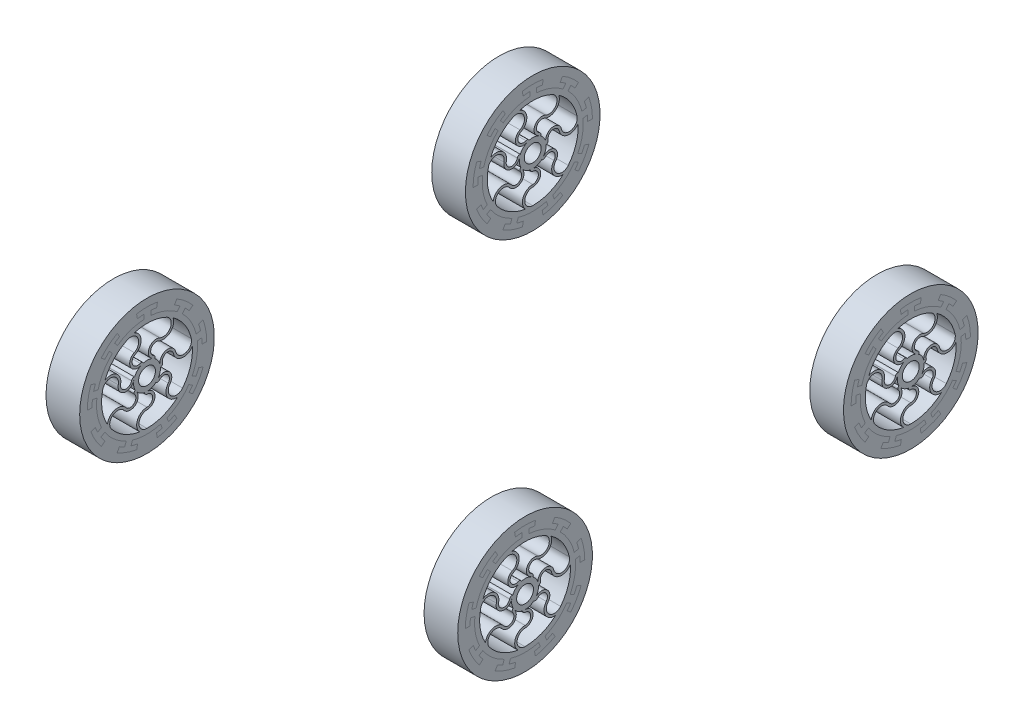
SolidWorks part; units mm, degrees
ref_plane "Front Plane" through (0, 0, 0) normal (0, 0, 1) x (1, 0, 0)
ref_plane "Top Plane" through (0, 0, 0) normal (0, 1, 0) x (1, 0, 0)
ref_plane "Right Plane" through (0, 0, 0) normal (1, 0, 0) x (0, 0, -1)
ref_plane "Plane1" through (64.95, 0, 0) normal (1, 0, 0) x (0, 0, -1)
sketch "Sketch1" plane through (64.95, 0, 0) normal (1, 0, 0) x (0, 0, -1)
  circle A0 centre (0, 0) radius 25.4 construction
  circle A1 centre (0, 0) radius 3.175
  circle A2 centre (0, 0) radius 5.08
  circle A3 centre (0, 0) radius 19.05
  circle A4 centre (0, 0) radius 17.145
  dimension "D1" = 50.8
  dimension "D2" = 38.1
  dimension "D3" = 34.29
  dimension "D4" = 6.35
  dimension "D5" = 10.16
extrude "Boss-Extrude1" add sketch "Sketch1" along normal blind 12.7 contours A3 A4 | A2 A1 region at (64.95, 0, 4.9363) region at (64.95, 0, 18.5112)
sketch "Sketch2" plane through (64.95, 0, 0) normal (1, 0, 0) x (0, 0, -1)
  circle A0 centre (0, 0) radius 5.08
  circle A1 centre (0, 0) radius 17.145
  arc A2 (0, -11.1125) -> (0, -5.08) centre (0, -8.0963) ccw
  arc A3 (0, -11.1125) -> (0, -17.145) centre (0, -14.1288) ccw
  arc A6 (0, -10.2235) -> (-2.7239, -16.9272) centre (0, -14.1288) ccw
  arc A7 (0, -10.2235) -> (0, -5.969) centre (0, -8.0963) ccw
  arc A8 (0, -5.969) -> (-0.8856, -5.0022) centre (0, -5.08) cw
  dimension "D1" = 10.16
  dimension "D2" = 34.29
  dimension "D3" = 0.889
  dimension "D4" = 0
extrude "Boss-Extrude2" add sketch "Sketch2" along normal up to surface (12.7 mm away) contours A8 A7 A6 A1 A3 A2 A0 region at (64.95, -10.6813, 0.5074) up to face at (77.65, 0, -3.175)
pattern_circular "CirPattern1" count 7 over 360 about axis through (77.65, 0, 0) along (1, 0, 0) of "Boss-Extrude2"
sketch "Sketch3" plane through (64.95, 0, 0) normal (1, 0, 0) x (0, 0, -1)
  line L2 (-3.9449, 22.1713) -> (-3.6335, 20.4208)
  line L4 (-1.1102, 20.7118) -> (-1.1102, 19.0176)
  line L6 (3.9449, 22.1713) -> (3.6335, 20.4208)
  line L7 (1.4298, 20.6921) -> (1.4298, 18.9963)
  circle A0 centre (0, 0) radius 19.05 construction
  circle A1 centre (0, 0) radius 19.05
  arc A2 (-3.9449, 22.1713) -> (3.9449, 22.1713) centre (0, 0) cw
  arc A3 (-3.6335, 20.4208) -> (-1.1102, 20.7118) centre (0, 0) cw
  arc A4 (1.4298, 20.6921) -> (3.6335, 20.4208) centre (0, 0) cw
  dimension "D5" = 2.5401
  dimension "D1" = 2.54
  dimension "D2" = 1.778
  dimension "D3" = 2.54
  dimension "D4" = 3.175
extrude "Boss-Extrude3" add sketch "Sketch3" along a picked direction on the side of the normal blind 12.7 contours A1 L7 L6 A2 L2 A3 L4 region at (64.95, 21.1336, -0.0386)
pattern_circular "CirPattern2" count 9 over 360 about axis through (77.65, 0, 0) along (1, 0, 0) of "Boss-Extrude3"
sketch "Sketch5" plane through (64.95, 0, 0) normal (1, 0, 0) x (0, 0, -1)
  line L36 (-1.1102, 20.7118) -> (-1.1102, 19.0176)
  line L37 (-3.9449, 22.1713) -> (-3.6335, 20.4208)
  line L38 (3.6335, 20.4208) -> (3.9449, 22.1713)
  line L39 (1.4298, 18.9963) -> (1.4298, 20.6921)
  line L40 (12.4628, 16.5797) -> (11.3738, 15.282)
  line L41 (11.2294, 19.5199) -> (10.3428, 17.9787)
  line L42 (15.9096, 13.3077) -> (17.2734, 14.4484)
  line L43 (13.3059, 13.6329) -> (14.396, 14.932)
  line L44 (20.2043, 4.6899) -> (18.5359, 4.3957)
  line L45 (21.1494, 7.735) -> (19.4796, 7.1243)
  line L46 (20.7415, -0.0322) -> (22.5195, -0.035)
  line L47 (18.956, 1.8906) -> (20.6261, 2.1851)
  line L48 (18.492, -9.3944) -> (17.0248, -8.5474)
  line L49 (21.1733, -7.6692) -> (19.5016, -7.0637)
  line L50 (15.8682, -13.357) -> (17.2284, -14.502)
  line L51 (15.7363, -10.7364) -> (17.205, -11.5843)
  line L52 (8.1271, -19.083) -> (7.5476, -17.491)
  line L53 (11.29, -19.4849) -> (10.3986, -17.9465)
  line L54 (3.57, -20.432) -> (3.876, -22.1834)
  line L55 (5.1535, -18.3397) -> (5.7335, -19.9333)
  line L56 (-6.0406, -19.8424) -> (-5.4612, -18.2504)
  line L57 (-3.876, -22.1834) -> (-3.57, -20.432)
  line L58 (-10.3986, -17.9465) -> (-11.29, -19.4849)
  line L59 (-7.8407, -17.3616) -> (-8.4207, -18.9552)
  line L60 (-17.3818, -11.3173) -> (-15.9147, -10.4703)
  line L61 (-17.2284, -14.502) -> (-15.8682, -13.357)
  line L62 (-19.5016, -7.0637) -> (-21.1733, -7.6692)
  line L63 (-17.1662, -8.2599) -> (-18.6348, -9.1078)
  line L64 (-20.5899, 2.5032) -> (-18.9215, 2.2091)
  line L65 (-22.5195, -0.035) -> (-20.7415, -0.0322)
  line L66 (-19.4796, 7.1243) -> (-21.1494, 7.735)
  line L67 (-18.4594, 4.7068) -> (-20.1295, 5.0013)
  line L68 (-14.1637, 15.1525) -> (-13.0747, 13.8547)
  line L69 (-17.2734, 14.4484) -> (-15.9096, 13.3077)
  line L70 (-10.3428, 17.9787) -> (-11.2294, 19.5199)
  line L71 (-11.1153, 15.4711) -> (-12.2054, 16.7702)
  line L72 (-1.1102, 20.7118) -> (-1.1102, 19.0176)
  line L73 (-3.9449, 22.1713) -> (-3.6335, 20.4208)
  line L74 (3.6335, 20.4208) -> (3.9449, 22.1713)
  line L75 (1.4298, 18.9963) -> (1.4298, 20.6921)
  line L76 (12.4628, 16.5797) -> (11.3738, 15.282)
  line L77 (11.2294, 19.5199) -> (10.3428, 17.9787)
  line L78 (15.9096, 13.3077) -> (17.2734, 14.4484)
  line L79 (13.3059, 13.6329) -> (14.396, 14.932)
  line L80 (20.2043, 4.6899) -> (18.5359, 4.3957)
  line L81 (21.1494, 7.735) -> (19.4796, 7.1243)
  line L82 (20.7415, -0.0322) -> (22.5195, -0.035)
  line L83 (18.956, 1.8906) -> (20.6261, 2.1851)
  line L84 (18.492, -9.3944) -> (17.0248, -8.5474)
  line L85 (21.1733, -7.6692) -> (19.5016, -7.0637)
  line L86 (15.8682, -13.357) -> (17.2284, -14.502)
  line L87 (15.7363, -10.7364) -> (17.205, -11.5843)
  line L88 (8.1271, -19.083) -> (7.5476, -17.491)
  line L89 (11.29, -19.4849) -> (10.3986, -17.9465)
  line L90 (3.57, -20.432) -> (3.876, -22.1834)
  line L91 (5.1535, -18.3397) -> (5.7335, -19.9333)
  line L92 (-6.0406, -19.8424) -> (-5.4612, -18.2504)
  line L93 (-3.876, -22.1834) -> (-3.57, -20.432)
  line L94 (-10.3986, -17.9465) -> (-11.29, -19.4849)
  line L95 (-7.8407, -17.3616) -> (-8.4207, -18.9552)
  line L96 (-17.3818, -11.3173) -> (-15.9147, -10.4703)
  line L97 (-17.2284, -14.502) -> (-15.8682, -13.357)
  line L98 (-19.5016, -7.0637) -> (-21.1733, -7.6692)
  line L99 (-17.1662, -8.2599) -> (-18.6348, -9.1078)
  line L100 (-20.5899, 2.5032) -> (-18.9215, 2.2091)
  line L101 (-22.5195, -0.035) -> (-20.7415, -0.0322)
  line L102 (-19.4796, 7.1243) -> (-21.1494, 7.735)
  line L103 (-18.4594, 4.7068) -> (-20.1295, 5.0013)
  line L104 (-14.1637, 15.1525) -> (-13.0747, 13.8547)
  line L105 (-17.2734, 14.4484) -> (-15.9096, 13.3077)
  line L106 (-10.3428, 17.9787) -> (-11.2294, 19.5199)
  line L107 (-11.1153, 15.4711) -> (-12.2054, 16.7702)
  circle A0 centre (0, 0) radius 25.4
  arc A37 (-1.1102, 19.0176) -> (-11.1153, 15.4711) centre (0, 0) ccw
  arc A38 (-1.1102, 20.7118) -> (-3.6335, 20.4208) centre (0, 0) ccw
  arc A39 (3.9449, 22.1713) -> (-3.9449, 22.1713) centre (0, 0) ccw
  arc A40 (3.6335, 20.4208) -> (1.4298, 20.6921) centre (0, 0) ccw
  arc A41 (11.3738, 15.282) -> (1.4298, 18.9963) centre (0, 0) ccw
  arc A42 (12.4628, 16.5797) -> (10.3428, 17.9787) centre (0, 0) ccw
  arc A43 (17.2734, 14.4484) -> (11.2294, 19.5199) centre (0, 0) ccw
  arc A44 (15.9096, 13.3077) -> (14.396, 14.932) centre (0, 0) ccw
  arc A45 (18.5359, 4.3957) -> (13.3059, 13.6329) centre (0, 0) ccw
  arc A46 (20.2043, 4.6899) -> (19.4796, 7.1243) centre (0, 0) ccw
  arc A47 (22.5195, -0.035) -> (21.1494, 7.735) centre (0, 0) ccw
  arc A48 (20.7415, -0.0322) -> (20.6261, 2.1851) centre (0, 0) ccw
  arc A49 (17.0248, -8.5474) -> (18.956, 1.8906) centre (0, 0) ccw
  arc A50 (18.492, -9.3944) -> (19.5016, -7.0637) centre (0, 0) ccw
  arc A51 (17.2284, -14.502) -> (21.1733, -7.6692) centre (0, 0) ccw
  arc A52 (15.8682, -13.357) -> (17.205, -11.5843) centre (0, 0) ccw
  arc A53 (7.5476, -17.491) -> (15.7363, -10.7364) centre (0, 0) ccw
  arc A54 (8.1271, -19.083) -> (10.3986, -17.9465) centre (0, 0) ccw
  arc A55 (3.876, -22.1834) -> (11.29, -19.4849) centre (0, 0) ccw
  arc A56 (3.57, -20.432) -> (5.7335, -19.9333) centre (0, 0) ccw
  arc A57 (-5.4612, -18.2504) -> (5.1535, -18.3397) centre (0, 0) ccw
  arc A58 (-6.0406, -19.8424) -> (-3.57, -20.432) centre (0, 0) ccw
  arc A59 (-11.29, -19.4849) -> (-3.876, -22.1834) centre (0, 0) ccw
  arc A60 (-10.3986, -17.9465) -> (-8.4207, -18.9552) centre (0, 0) ccw
  arc A61 (-15.9147, -10.4703) -> (-7.8407, -17.3616) centre (0, 0) ccw
  arc A62 (-17.3818, -11.3173) -> (-15.8682, -13.357) centre (0, 0) ccw
  arc A63 (-21.1733, -7.6692) -> (-17.2284, -14.502) centre (0, 0) ccw
  arc A64 (-19.5016, -7.0637) -> (-18.6348, -9.1078) centre (0, 0) ccw
  arc A65 (-18.9215, 2.2091) -> (-17.1662, -8.2599) centre (0, 0) ccw
  arc A66 (-20.5899, 2.5032) -> (-20.7415, -0.0322) centre (0, 0) ccw
  arc A67 (-21.1494, 7.735) -> (-22.5195, -0.035) centre (0, 0) ccw
  arc A68 (-19.4796, 7.1243) -> (-20.1295, 5.0013) centre (0, 0) ccw
  arc A69 (-13.0747, 13.8547) -> (-18.4594, 4.7068) centre (0, 0) ccw
  arc A70 (-14.1637, 15.1525) -> (-15.9096, 13.3077) centre (0, 0) ccw
  arc A71 (-11.2294, 19.5199) -> (-17.2734, 14.4484) centre (0, 0) ccw
  arc A72 (-10.3428, 17.9787) -> (-12.2054, 16.7702) centre (0, 0) ccw
  arc A73 (-1.1102, 19.0176) -> (-11.1153, 15.4711) centre (0, 0) ccw
  arc A74 (-1.1102, 20.7118) -> (-3.6335, 20.4208) centre (0, 0) ccw
  arc A75 (3.9449, 22.1713) -> (-3.9449, 22.1713) centre (0, 0) ccw
  arc A76 (3.6335, 20.4208) -> (1.4298, 20.6921) centre (0, 0) ccw
  arc A77 (11.3738, 15.282) -> (1.4298, 18.9963) centre (0, 0) ccw
  arc A78 (12.4628, 16.5797) -> (10.3428, 17.9787) centre (0, 0) ccw
  arc A79 (17.2734, 14.4484) -> (11.2294, 19.5199) centre (0, 0) ccw
  arc A80 (15.9096, 13.3077) -> (14.396, 14.932) centre (0, 0) ccw
  arc A81 (18.5359, 4.3957) -> (13.3059, 13.6329) centre (0, 0) ccw
  arc A82 (20.2043, 4.6899) -> (19.4796, 7.1243) centre (0, 0) ccw
  arc A83 (22.5195, -0.035) -> (21.1494, 7.735) centre (0, 0) ccw
  arc A84 (20.7415, -0.0322) -> (20.6261, 2.1851) centre (0, 0) ccw
  arc A85 (17.0248, -8.5474) -> (18.956, 1.8906) centre (0, 0) ccw
  arc A86 (18.492, -9.3944) -> (19.5016, -7.0637) centre (0, 0) ccw
  arc A87 (17.2284, -14.502) -> (21.1733, -7.6692) centre (0, 0) ccw
  arc A88 (15.8682, -13.357) -> (17.205, -11.5843) centre (0, 0) ccw
  arc A89 (7.5476, -17.491) -> (15.7363, -10.7364) centre (0, 0) ccw
  arc A90 (8.1271, -19.083) -> (10.3986, -17.9465) centre (0, 0) ccw
  arc A91 (3.876, -22.1834) -> (11.29, -19.4849) centre (0, 0) ccw
  arc A92 (3.57, -20.432) -> (5.7335, -19.9333) centre (0, 0) ccw
  arc A93 (-5.4612, -18.2504) -> (5.1535, -18.3397) centre (0, 0) ccw
  arc A94 (-6.0406, -19.8424) -> (-3.57, -20.432) centre (0, 0) ccw
  arc A95 (-11.29, -19.4849) -> (-3.876, -22.1834) centre (0, 0) ccw
  arc A96 (-10.3986, -17.9465) -> (-8.4207, -18.9552) centre (0, 0) ccw
  arc A97 (-15.9147, -10.4703) -> (-7.8407, -17.3616) centre (0, 0) ccw
  arc A98 (-17.3818, -11.3173) -> (-15.8682, -13.357) centre (0, 0) ccw
  arc A99 (-21.1733, -7.6692) -> (-17.2284, -14.502) centre (0, 0) ccw
  arc A100 (-19.5016, -7.0637) -> (-18.6348, -9.1078) centre (0, 0) ccw
  arc A101 (-18.9215, 2.2091) -> (-17.1662, -8.2599) centre (0, 0) ccw
  arc A102 (-20.5899, 2.5032) -> (-20.7415, -0.0322) centre (0, 0) ccw
  arc A103 (-21.1494, 7.735) -> (-22.5195, -0.035) centre (0, 0) ccw
  arc A104 (-19.4796, 7.1243) -> (-20.1295, 5.0013) centre (0, 0) ccw
  arc A105 (-13.0747, 13.8547) -> (-18.4594, 4.7068) centre (0, 0) ccw
  arc A106 (-14.1637, 15.1525) -> (-15.9096, 13.3077) centre (0, 0) ccw
  arc A107 (-11.2294, 19.5199) -> (-17.2734, 14.4484) centre (0, 0) ccw
  arc A108 (-10.3428, 17.9787) -> (-12.2054, 16.7702) centre (0, 0) ccw
  dimension "D1" = 50.8
  dimension "D2" = 0
extrude "Boss-Extrude4" add sketch "Sketch5" along normal up to surface (12.7 mm away) separate body up to face at (77.65, -8.4949, 4.395)
sketch "Sketch4" plane through (0, 0, 0) normal (1, 0, 0) x (0, 0, -1)
  line L0 (0, 0) -> (-145.5, 0) construction
pattern_linear "LPattern1" count 2 spacing 145.5 along (0, 0, 1) of bodies 111 107
mirror "Mirror1" about plane through (0, 0, 0) normal (1, 0, 0) of bodies 107 108 112 111
